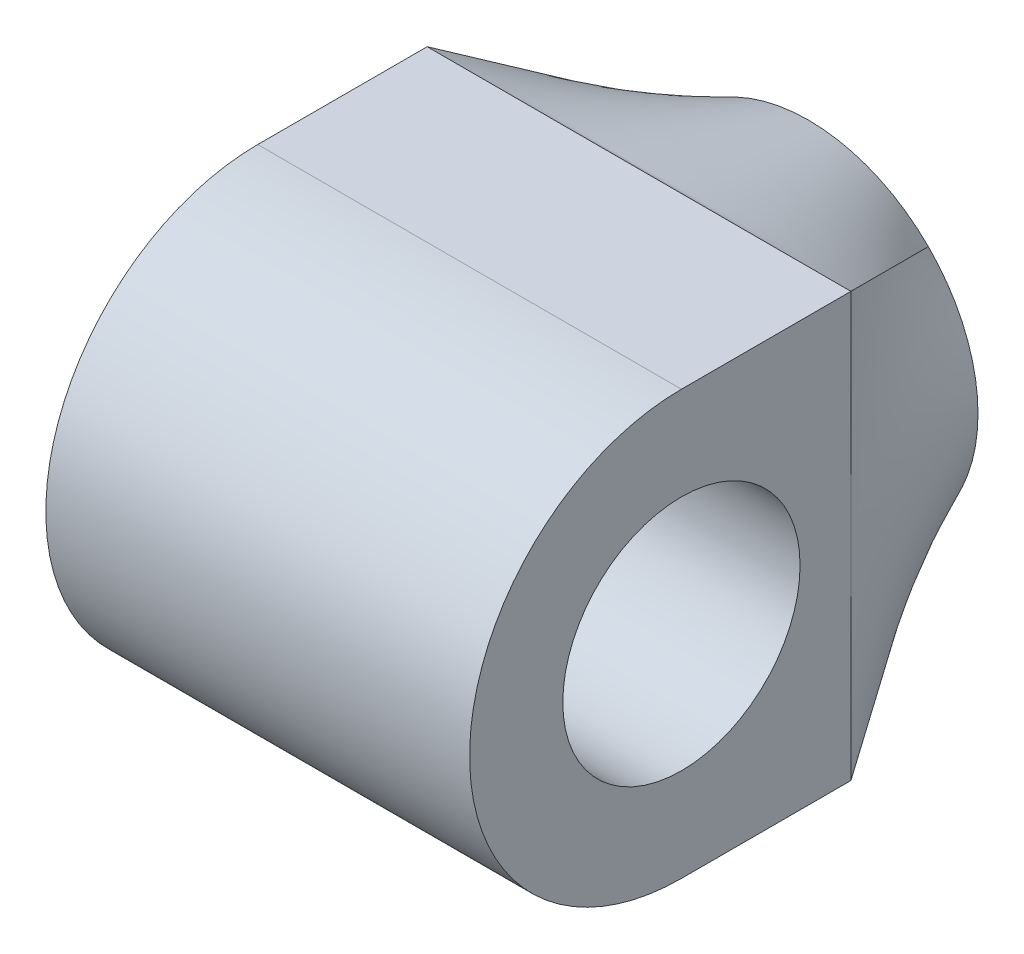
SolidWorks part; units mm, degrees
material "Maraging"
ref_plane "Front Plane" through (0, 0, 0) normal (0, 0, 1) x (1, 0, 0)
ref_plane "Top Plane" through (0, 0, 0) normal (0, 1, 0) x (1, 0, 0)
ref_plane "Right Plane" through (0, 0, 0) normal (1, 0, 0) x (0, 0, -1)
sketch "Sketch1" plane through (0, 0, 0) normal (0, 0, 1) x (1, 0, 0)
  circle A0 centre (0, 0) radius 10
  dimension "D1" = 20
ref_plane "Plane1" through (0, 0, 10) normal (0, 0, 1) x (1, 0, 0)
sketch "Sketch2" plane through (0, 0, 10) normal (0, 0, 1) x (1, 0, 0)
  line L1 (-12.5, -12.5) -> (12.5, -12.5)
  line L2 (-12.5, -12.5) -> (-12.5, 12.5)
  line L3 (-12.5, 12.5) -> (12.5, 12.5)
  line L4 (12.5, -12.5) -> (12.5, 12.5)
  line L5 (-12.5, -12.5) -> (12.5, 12.5) construction
  line L6 (-12.5, 12.5) -> (12.5, -12.5) construction
  point P0 (0, 0)
  dimension "D1" = 25
loft "Loft1" add profiles "Sketch2", "Sketch1"
sketch "Sketch3" plane through (0, 0, 0) normal (1, 0, 0) x (0, 0, -1)
  line L0 (-10, 12.5) -> (-20, 12.5)
  line L1 (-20, -12.5) -> (-10, -12.5)
  line L2 (-10, -12.5) -> (-10, 12.5)
  arc A0 (-20, 12.5) -> (-20, -12.5) centre (-20, 0) ccw
  dimension "D1" = 10
extrude "Boss-Extrude1" add sketch "Sketch3" along normal through all and the other way through all
sketch "Sketch4" plane through (12.5017, 0, 0) normal (1, 0, 0) x (0, 0, -1)
  circle A0 centre (-20, 0) radius 7
  arc A1 (-20, 12.5) -> (-20, -12.5) centre (-20, 0) ccw construction
  dimension "D1" = 14
extrude "Cut-Extrude1" cut sketch "Sketch4" against normal blind 10
